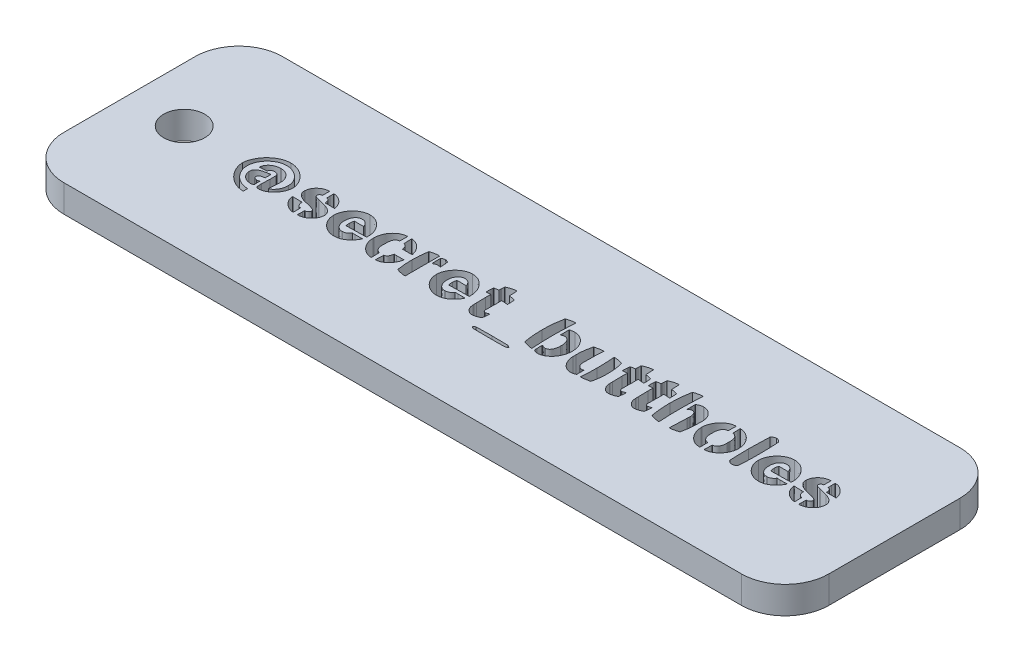
SolidWorks part; units mm, degrees
ref_plane "Front Plane" through (0, 0, 0) normal (0, 0, 1) x (1, 0, 0)
ref_plane "Top Plane" through (0, 0, 0) normal (0, 1, 0) x (1, 0, 0)
ref_plane "Right Plane" through (0, 0, 0) normal (1, 0, 0) x (0, 0, -1)
sketch "Sketch1" plane through (0, 0, 0) normal (0, 1, 0) x (1, 0, 0)
  line L1 (-22.225, -6.35) -> (22.225, -6.35)
  line L2 (-22.225, -6.35) -> (-22.225, 6.35)
  line L3 (-22.225, 6.35) -> (22.225, 6.35)
  line L4 (22.225, -6.35) -> (22.225, 6.35)
  line L5 (-22.225, -6.35) -> (22.225, 6.35) construction
  line L6 (-22.225, 6.35) -> (22.225, -6.35) construction
  point P0 (0, 0)
  dimension "D1" = 12.7
  dimension "D2" = 44.45
extrude "Boss-Extrude1" add sketch "Sketch1" along normal blind 1.5875
fillet "Fillet1" radius 2.54 4 edges at (-22.225, 0.7937, -6.35) (-22.225, 0.7937, 6.35) (22.225, 0.7937, -6.35) (22.225, 0.7937, 6.35)
hole_wizard "3/32 (0.09375) Diameter Hole1" positions "Sketch2" profile "Sketch3" hole size "3/32" standard "ANSI Inch" end condition through all
sketch "Sketch2" plane through (0, 0, 0) normal (0, -1, 0) x (-1, 0, 0)
  line L0 (19.05, 6.35) -> (19.05, -6.35) construction
  line L1 (-19.685, 6.35) -> (19.685, 6.35) construction
  line L2 (19.685, -6.35) -> (-19.685, -6.35) construction
  line L4 (22.225, 3.81) -> (22.225, -3.81) construction
  point P11 (19.05, 0)
  dimension "D1" = 3.175
sketch "Sketch3" plane through (-19.05, 0, 0) normal (1, 0, 0) x (0, 0, -1)
  line L0 (0, 0) -> (0, 1.5875)
  line L1 (0, 1.5875) -> (1.1906, 1.5875)
  line L2 (1.1906, 1.5875) -> (1.1906, 0)
  line L5 (1.1906, 0) -> (0, 0)
  line L11 (0, -6.35) -> (0, 107.95) construction
  dimension "Thru Hole Dia." = 2.3812
  dimension "Thru Hole Depth" = 1.5875
sketch "Sketch4" plane through (0, 0, 0) normal (0, -1, 0) x (1, 0, 0)
  line L0 (22.225, 1.1602) -> (-22.225, 1.1602) construction
  line L1 (22.225, 3.81) -> (22.225, -3.81) construction
  line L2 (-22.225, -3.81) -> (-22.225, 3.81) construction
  text T0 "@secret_buttholes   " font "Stencilia-Bold" height in points 8
  point P7 (0, 0)
  point P8 (-22.225, 5.8581)
extrude "Cut-Extrude1" cut sketch "Sketch4" against normal through all
